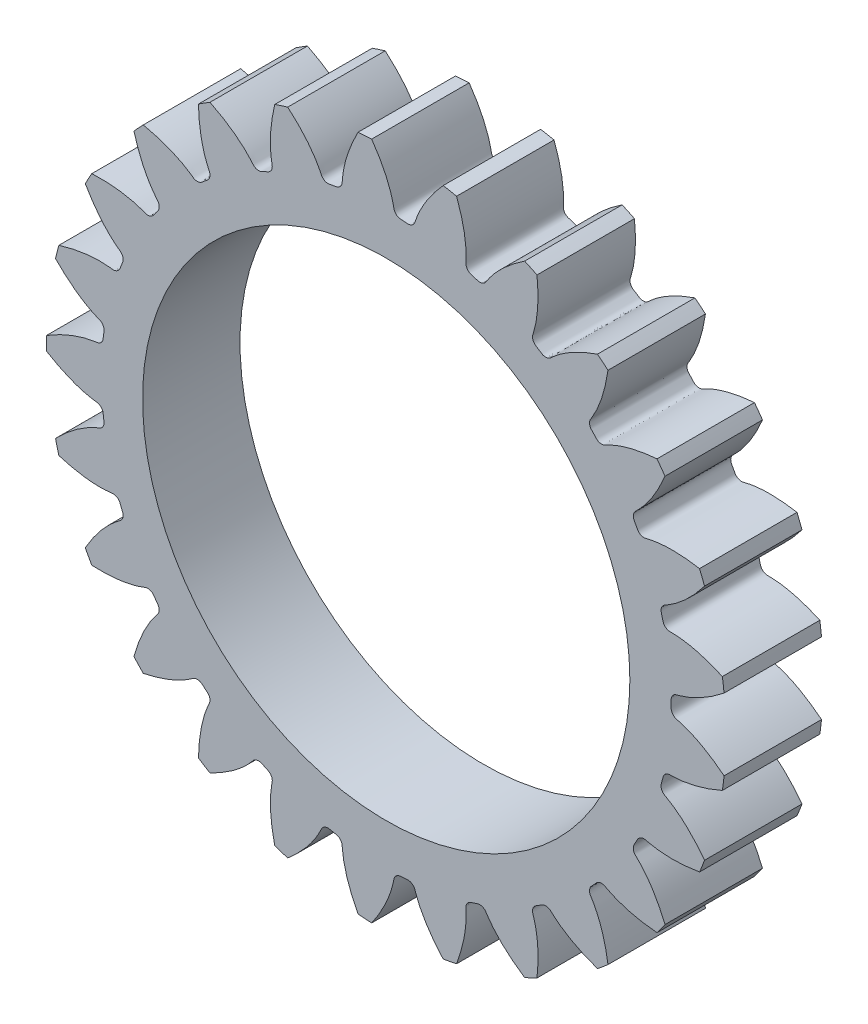
SolidWorks part; units mm, degrees
ref_plane "Front Plane" through (0, 0, 0) normal (0, 0, 1) x (1, 0, 0)
ref_plane "Top Plane" through (0, 0, 0) normal (0, 1, 0) x (1, 0, 0)
ref_plane "Right Plane" through (0, 0, 0) normal (1, 0, 0) x (0, 0, -1)
ref_axis "Axis1" through (0, 0, 55) along (0, 0, -1)
sketch "SketchRevolveSpurGear" plane through (0, 0, 0) normal (1, 0, 0) x (0, 0, -1)
  line L0 (0, 0) -> (1, 0) construction
  line L1 (-2, 0) -> (-2, 13.9435)
  line L2 (-2, 13.9435) -> (2, 13.9435)
  line L3 (2, 13.9435) -> (2, 0)
  line L4 (2, 0) -> (-2, 0)
  dimension "Side1" = 2
  dimension "OutsideRadius" = 13.9435
  dimension "Side2" = 2
revolve "SpurGear" add sketch "SketchRevolveSpurGear" angle 360 about L0
sketch "SketchToothSpurGear" plane through (0, 0, 0) normal (0, 0, 1) x (1, 0, 0)
  arc A0 (13.9327, 1.5237) -> (13.9327, -1.5237) centre (0, 0) cw
  spline S0 degree 3 poles (13.9327, -1.5237) (13.8433, -1.4505) (13.7093, -1.3458) (13.5292, -1.2152) (13.4, -1.126) (13.2741, -1.0435) (13.1518, -0.9673) (13.0333, -0.8973) (12.9189, -0.8334) (12.8087, -0.7751) (12.7031, -0.7224) (12.6021, -0.6749) (12.5059, -0.6324) (12.4148, -0.5947) (12.3289, -0.5615) (12.2483, -0.5324) (12.1732, -0.5074) (12.0613, -0.4726) (11.9568, -0.4485) (11.863, -0.4155) (11.8208, -0.3907) (11.783, -0.3596) (11.7507, -0.3228) (11.7248, -0.2813) (11.7061, -0.2361) (11.6945, -0.1885) (11.691, -0.1093) (11.6954, 0) (11.691, 0.1093) (11.6945, 0.1885) (11.7061, 0.2361) (11.7248, 0.2813) (11.7507, 0.3228) (11.783, 0.3596) (11.8208, 0.3907) (11.863, 0.4155) (11.9568, 0.4485) (12.0613, 0.4726) (12.1732, 0.5074) (12.2483, 0.5324) (12.3289, 0.5615) (12.4148, 0.5947) (12.5059, 0.6324) (12.6021, 0.6749) (12.7031, 0.7224) (12.8087, 0.7751) (12.9189, 0.8334) (13.0333, 0.8973) (13.1518, 0.9673) (13.2741, 1.0435) (13.4, 1.126) (13.5292, 1.2152) (13.7093, 1.3458) (13.8433, 1.4505) (13.9327, 1.5237) knots 0 0 0 0 0.060855 0.089572 0.11715 0.143587 0.168884 0.193042 0.216059 0.237936 0.258673 0.27827 0.296727 0.314043 0.33022 0.345257 0.359153 0.37191 0.407022 0.415578 0.424134 0.43269 0.441247 0.449803 0.458359 0.466915 0.475471 0.5 0.524529 0.533085 0.541641 0.550197 0.558753 0.56731 0.575866 0.584422 0.592978 0.62809 0.640847 0.654743 0.66978 0.685957 0.703273 0.72173 0.741327 0.762064 0.783941 0.806958 0.831116 0.856413 0.88285 0.910428 0.939145 1 1 1 1
extrude "ToothExtrudeCutSpurGear" cut sketch "SketchToothSpurGear" against normal blind 2 and the other way blind 2
pattern_circular "PatternSpurGear" count 25 every 14.4 about axis through (0, 0, 55) along (0, 0, -1) of "ToothExtrudeCutSpurGear"
sketch "BoreRevolveSketch" plane through (0, 0, 0) normal (1, 0, 0) x (0, 0, -1)
  line L0 (0, 0) -> (1, 0) construction
  line L1 (-2, 0) -> (2, 0)
  line L2 (2, 0) -> (2, 10)
  line L3 (2, 10) -> (-2, 10)
  line L4 (-2, 10) -> (-2, 0)
  dimension "BoreSide1" = 2
  dimension "TaperSide1" = 10
  dimension "BoreSide2" = 2
  dimension "TaperSide2" = 10
revolve "BoreRevolveCut" cut sketch "BoreRevolveSketch" angle 360 about L0
sketch "AuxiliarySketchSpurGear" plane through (0, 0, 0) normal (0, 0, 1) x (1, 0, 0)
  circle A0 centre (0, 0) radius 12.5 construction
  circle A1 centre (0, 0) radius 11.7462 construction
  circle A2 centre (0, 0) radius 12.0081 construction
  circle A3 centre (0, 0) radius 13.9435 construction
  circle A4 centre (0, 0) radius 11.6935 construction
  dimension "PitchDiameter" = 25
  dimension "BaseDiameter" = 23.4923
  dimension "FormDiameter" = 24.0162
  dimension "MajorDiameter" = 27.8871
  dimension "MinorDiameter" = 23.3871
